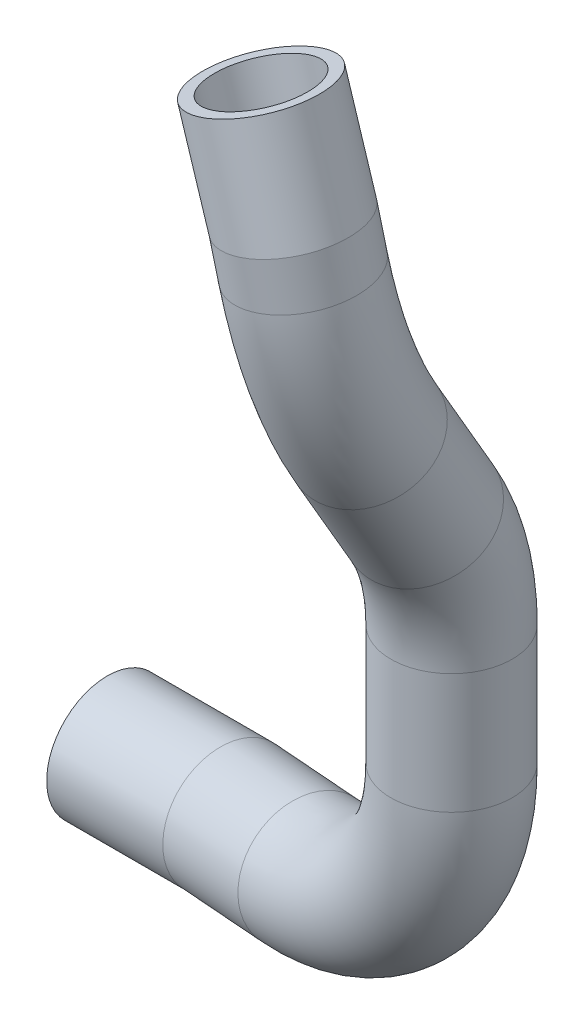
SolidWorks part; units mm, degrees
material "Kauczuk krzemowy"
ref_plane "Płaszczyzna przednia" through (0, 0, 0) normal (0, 0, 1) x (1, 0, 0)
ref_plane "Płaszczyzna górna" through (0, 0, 0) normal (0, 1, 0) x (1, 0, 0)
ref_plane "Płaszczyzna prawa" through (0, 0, 0) normal (1, 0, 0) x (0, 0, -1)
sketch3d "Szkic 3D1"
  line L1 (1122.6627, -353.961, 132.6671) -> (1124.1426, -362.624, 132.045)
  line L2 (1124.9907, -465.2567, 102.3034) -> (1124.9907, -440.5046, 102.3034)
  line L3 (1126.4816, -396.3402, 121.3206) -> (1125.4954, -417.2774, 108.7415)
  line L5 (1122.6627, -353.961, 132.6671) -> (1115.9855, -333.1594, 132.5648)
  line L6 (1044.71, -507.0217, 92.9945) -> (1069.71, -507.0217, 92.9945)
  line L7 (1069.71, -507.0217, 92.9945) -> (1089.3923, -505.0661, 96.3089)
  arc A0 (1126.4816, -396.3402, 121.3206) -> (1124.1426, -362.624, 132.045) centre (1097.4629, -362.5349, 67.3288) ccw
  arc A2 (1124.9907, -465.2567, 102.3034) -> (1089.3923, -505.0661, 96.3089) centre (1085.546, -465.2567, 95.6612) ccw
  arc A4 (1125.4954, -417.2774, 108.7415) -> (1124.9907, -440.5046, 102.3034) centre (1128.5079, -440.5046, 147.1657) ccw
  point P1 (1119.3241, -343.5602, 132.6159)
  point P5 (1124.9907, -501.5292, 102.3034)
  point P7 (1127.221, -380.6438, 130.7511)
  point P9 (1033.8238, -375.2892, 93.5469)
  point P10 (0, 0, 0)
  point P16 (1124.9907, -501.5292, 102.3034)
  point P24 (1124.9907, -427.9933, 102.3034)
  point P25 (1083.6456, -440.5046, 150.6829)
  point P30 (1092.1883, -465.2567, 56.2165)
  dimension "D2" = 40
  dimension "D3" = 56.3274
sweep "Wyciągnięcie po ścieżce-Cienka ścianka1" add path "Szkic 3D1" circular profile diameter 25 parameters "D1"=2.5, "D3"=25
